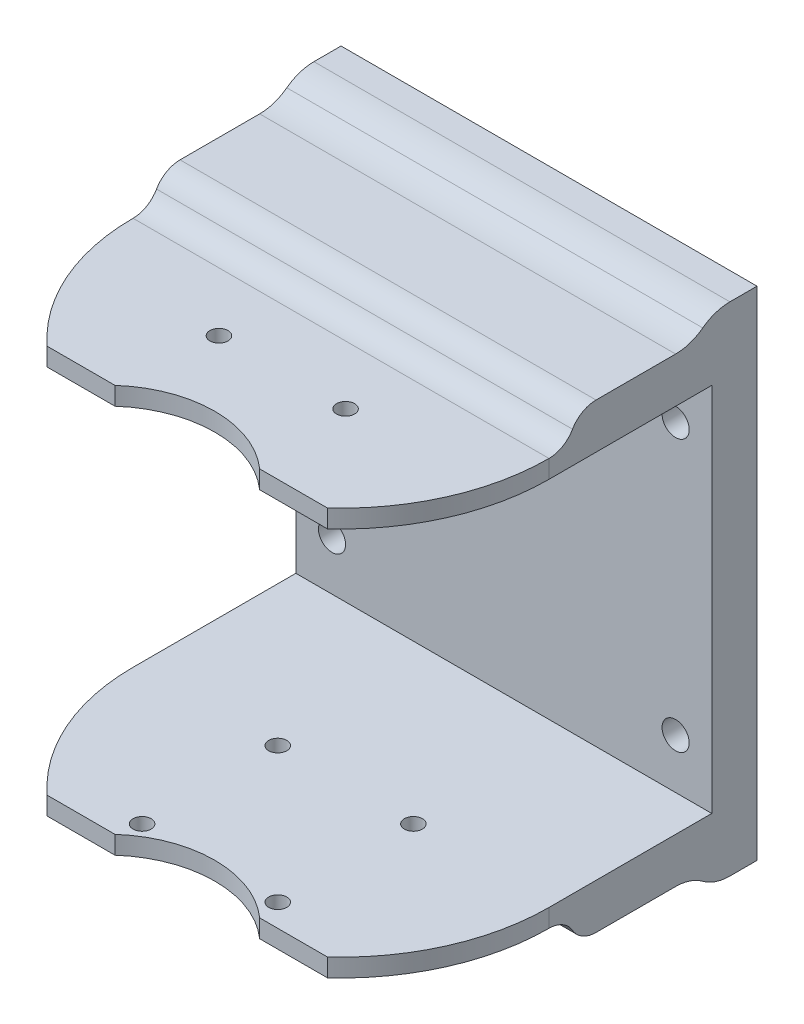
SolidWorks part; units mm, degrees
ref_plane "前视基准面" through (0, 0, 0) normal (0, 0, 1) x (1, 0, 0)
ref_plane "上视基准面" through (0, 0, 0) normal (0, 1, 0) x (1, 0, 0)
ref_plane "右视基准面" through (0, 0, 0) normal (1, 0, 0) x (0, 0, -1)
other "Configuration Table"
sketch "草图1" plane through (0, 0, 0) normal (0, 0, 1) x (1, 0, 0)
  line L0 (0, 20) -> (0, -20) construction
  line L1 (-23, 20) -> (23, 20)
  line L2 (-23, 20) -> (-23, -20)
  line L3 (-23, -20) -> (23, -20)
  line L4 (23, 20) -> (23, -20)
  line L5 (-23, 20) -> (23, -20) construction
  line L6 (-23, -20) -> (23, 20) construction
  line L7 (-23, 0) -> (23, 0) construction
  circle A0 centre (-19, 15) radius 1.5
  circle A1 centre (19, 15) radius 1.5
  circle A2 centre (19, -15) radius 1.5
  circle A3 centre (-19, -15) radius 1.5
  point P0 (0, 0)
  dimension "D3" = 3
  dimension "D1" = 46
  dimension "D2" = 40
  dimension "D4" = 19
  dimension "D5" = 15
extrude "凸台-拉伸1" add sketch "草图1" along normal blind 5
sketch "草图2" plane through (0, 0, 5) normal (0, 0, 1) x (1, 0, 0)
  line L0 (0, 20) -> (0, -20) construction
  line L1 (23, 20) -> (-23, 20) construction
  line L2 (-23, -20) -> (23, -20) construction
  line L3 (-23, 0) -> (23, 0) construction
  line L8 (-23, 20) -> (-23, -20) construction
  line L9 (23, -20) -> (23, 20) construction
  line L10 (-23, -27.5) -> (23, -27.5)
  line L11 (-23, 20) -> (23, 20)
  line L12 (-23, 20) -> (-23, 27.5)
  line L13 (-23, 27.5) -> (23, 27.5)
  line L14 (23, 20) -> (23, 27.5)
  line L15 (23, -20) -> (23, -27.5)
  line L16 (-23, -20) -> (23, -20)
  line L17 (-23, -20) -> (-23, -27.5)
  dimension "D1" = 7.5
  dimension "D2" = 0
extrude "凸台-拉伸2" add sketch "草图2" against normal blind 5
sketch "草图3" plane through (0, 0, 5) normal (0, 0, 1) x (1, 0, 0)
  line L0 (0, 27.5) -> (0, -27.5) construction
  line L1 (23, 27.5) -> (-23, 27.5) construction
  line L2 (-23, -27.5) -> (23, -27.5) construction
  line L3 (-23, 0) -> (23, 0) construction
  line L4 (-23, 27.5) -> (-23, -27.5) construction
  line L5 (23, -27.5) -> (23, 27.5) construction
  line L6 (-23, -20.5) -> (23, -20.5)
  line L7 (-23, 25.5) -> (23, 25.5)
  line L8 (-23, 25.5) -> (-23, 20.5)
  line L9 (-23, 20.5) -> (23, 20.5)
  line L10 (23, 25.5) -> (23, 20.5)
  line L11 (23, -25.5) -> (23, -20.5)
  line L12 (-23, -25.5) -> (23, -25.5)
  line L13 (-23, -25.5) -> (-23, -20.5)
  dimension "D1" = 20.5
  dimension "D2" = 5
  dimension "D3" = 0
extrude "凸台-拉伸3" add sketch "草图3" along normal blind 15
fillet "圆角1" radius 5 2 edges at (0, -25.5, 5) (0, 25.5, 5)
fillet "圆角2" radius 5 2 edges at (0, 27.5, 5) (0, -27.5, 5)
sketch "草图4" plane through (0, 0, 20) normal (0, 0, 1) x (1, 0, 0)
  line L0 (0, 25.5) -> (0, -20.5) construction
  line L1 (23, 25.5) -> (-23, 25.5) construction
  line L2 (23, -20.5) -> (-23, -20.5) construction
  line L3 (-23, 20.5) -> (23, 20.5) construction
  line L4 (-23, 20.5) -> (23, 20.5)
  line L5 (-23, 20.5) -> (-23, 22.5)
  line L6 (-23, 22.5) -> (23, 22.5)
  line L7 (23, 20.5) -> (23, 22.5)
  line L8 (-23, 0) -> (23, 0) construction
  line L9 (-23, 20.5) -> (-23, -20.5) construction
  line L10 (23, -20.5) -> (23, 20.5) construction
  line L11 (-23, -22.5) -> (23, -22.5)
  line L12 (23, -20.5) -> (23, -22.5)
  line L13 (-23, -20.5) -> (23, -20.5)
  line L14 (-23, -20.5) -> (-23, -22.5)
  line L15 (-23, 25.5) -> (-23, 20.5) construction
  dimension "D1" = 2
  dimension "D2" = 0
extrude "凸台-拉伸4" add sketch "草图4" along normal blind 20
sketch "草图5" plane through (0, -22.5, 0) normal (0, -1, 0) x (1, 0, 0)
  line L0 (0, 20) -> (0, 40) construction
  line L1 (-23, 20) -> (23, 20) construction
  line L2 (-23, 40) -> (23, 40) construction
  line L3 (-23, 30) -> (23, 30) construction
  line L4 (-23, 40) -> (-23, 20) construction
  line L5 (23, 40) -> (23, 20) construction
  line L7 (-7.5, 37.5) -> (7.5, 37.5) construction
  line L8 (-7.5, 37.5) -> (-7.5, 22.5) construction
  line L9 (-7.5, 22.5) -> (7.5, 22.5) construction
  line L10 (7.5, 37.5) -> (7.5, 22.5) construction
  line L11 (-7.5, 37.5) -> (7.5, 22.5) construction
  line L12 (-7.5, 22.5) -> (7.5, 37.5) construction
  circle A0 centre (-7.5, 37.5) radius 1
  circle A1 centre (7.5, 37.5) radius 1
  circle A2 centre (-7.5, 22.5) radius 1
  circle A3 centre (7.5, 22.5) radius 1
  point P12 (0, 30)
  dimension "D3" = 2
  dimension "D1" = 15
  dimension "D2" = 15
extrude "切除-拉伸1" cut sketch "草图5" against normal blind 2
sketch "草图6" plane through (0, 20.5, 0) normal (0, -1, 0) x (1, 0, 0)
  line L0 (-7.5, 22.5) -> (7.5, 22.5) construction
  line L1 (-15.0231, 29.5) -> (14.1961, 29.5) construction
  line L2 (0, 0) -> (0, 40) construction
  line L3 (-23, 40) -> (23, 40) construction
  circle A0 centre (7, 29.5) radius 1
  circle A1 centre (-7, 29.5) radius 1
  dimension "D2" = 7
  dimension "D3" = 2
  dimension "D1" = 7
extrude "切除-拉伸2" cut sketch "草图6" against normal blind 2
fillet "圆角3" radius 3 2 edges at (0, -22.5, 20) (0, 22.5, 20)
fillet "圆角4" radius 3 2 edges at (0, 25.5, 20) (0, -25.5, 20)
sketch "草图7" plane through (0, -22.5, 0) normal (0, -1, 0) x (1, 0, 0)
  line L0 (0, 40) -> (0, 0) construction
  line L1 (-23, 40) -> (23, 40) construction
  line L2 (0, 40) -> (0, 59.8426) construction
  line L3 (-8, 40) -> (8, 40)
  line L18 (-6.634, 23) -> (6.634, 23) construction
  line L19 (-23, 23) -> (-23, 40)
  line L20 (-23, 40) -> (-15.4919, 40)
  line L21 (23, 23) -> (23, 40)
  line L22 (23, 40) -> (15.4919, 40)
  arc A0 (-8, 40) -> (8, 40) centre (0, 49) ccw
  arc A1 (-23, 23) -> (-15.4919, 40) centre (0, 23) cw
  arc A6 (23, 23) -> (15.4919, 40) centre (0, 23) ccw
  dimension "D1" = 8
  dimension "D2" = 9
extrude "切除-拉伸3" cut sketch "草图7" against normal up to surface (45 mm away) up to face at (8, 22.5, 29.5)
